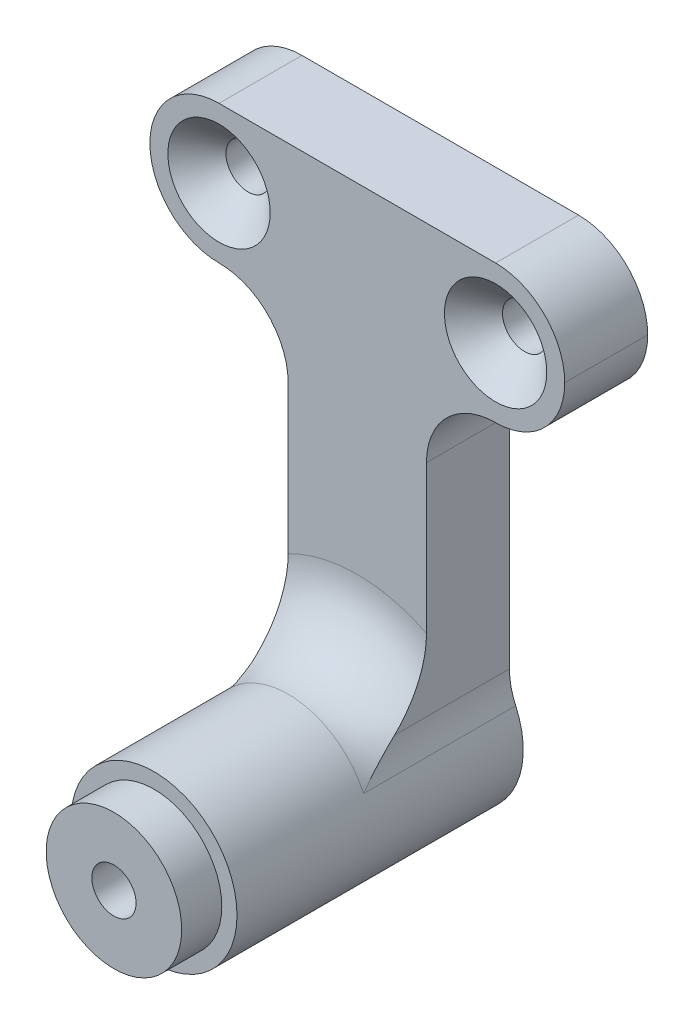
SolidWorks part; units mm, degrees
ref_plane "Plan de face" through (0, 0, 0) normal (0, 0, 1) x (1, 0, 0)
ref_plane "Plan de dessus" through (0, 0, 0) normal (0, 1, 0) x (1, 0, 0)
ref_plane "Plan de droite" through (0, 0, 0) normal (1, 0, 0) x (0, 0, -1)
sketch "Esquisse1" plane through (0, 0, 0) normal (0, 0, 1) x (1, 0, 0)
  line L0 (-5, 25.5) -> (-5, 3.3166)
  line L1 (-15, 35.5) -> (15, 35.5)
  line L2 (-15, 35.5) -> (-15, 25.5)
  line L3 (-15, 25.5) -> (-5, 25.5)
  line L4 (15, 35.5) -> (15, 25.5)
  line L5 (5, 25.5) -> (5, 3.3166)
  line L6 (5, 25.5) -> (15, 25.5)
  arc A0 (-5, 3.3166) -> (5, 3.3166) centre (0, 0) ccw
  dimension "D1" = 12
  dimension "D2" = 30
  dimension "D3" = 10
  dimension "D4" = 15
  dimension "D5" = 35.5
  dimension "D6" = 10
  dimension "D7" = 5
extrude "Boss.-Extru.1" add sketch "Esquisse1" along normal blind 6
sketch "Esquisse2" plane through (0, 0, 6) normal (0, 0, 1) x (1, 0, 0)
  circle A0 centre (0, 0) radius 6
extrude "Boss.-Extru.2" add sketch "Esquisse2" along normal blind 14.7
sketch "Esquisse3" plane through (0, 0, 20.7) normal (0, 0, 1) x (1, 0, 0)
  circle A0 centre (0, 0) radius 4.9
  dimension "D1" = 9.8
extrude "Boss.-Extru.3" add sketch "Esquisse3" along normal blind 2.9
sketch "Esquisse4" plane through (0, 0, 0) normal (0, 0, -1) x (-1, 0, 0)
  circle A0 centre (0, 0) radius 1.6
  dimension "D1" = 3.2
extrude "Enlèv. mat.-Extru.1" cut sketch "Esquisse4" against normal through all
chamfer "Chanfrein1" distance 2.1 angle 45 1 edges at (-1.6, 0, 0)
sketch "Esquisse6" plane through (0, 0, 6) normal (0, 0, 1) x (1, 0, 0)
  line L0 (-15, 35.5) -> (-15, 25.5) construction
  line L1 (15, 35.5) -> (-15, 35.5) construction
  line L2 (15, 25.5) -> (15, 35.5) construction
  circle A0 centre (-10, 30.5) radius 1.6
  circle A1 centre (10, 30.5) radius 1.6
  dimension "D1" = 3.2
  dimension "D2" = 3.2
  dimension "D3" = 5
  dimension "D4" = 5
  dimension "D5" = 5
  dimension "D6" = 5
extrude "Enlèv. mat.-Extru.2" cut sketch "Esquisse6" against normal through all
fillet "Congé1" radius 5 8 edges at (5, 25.5, 3) (15, 25.5, 3) (15, 35.5, 3) (-15, 35.5, 3) (-15, 25.5, 3) (-5, 25.5, 3)
chamfer "Chanfrein2" distance 2.1 angle 45 2 edges at (11.6, 30.5, 6) (-8.4, 30.5, 6)
fillet "Congé2" radius 5 1 edges
